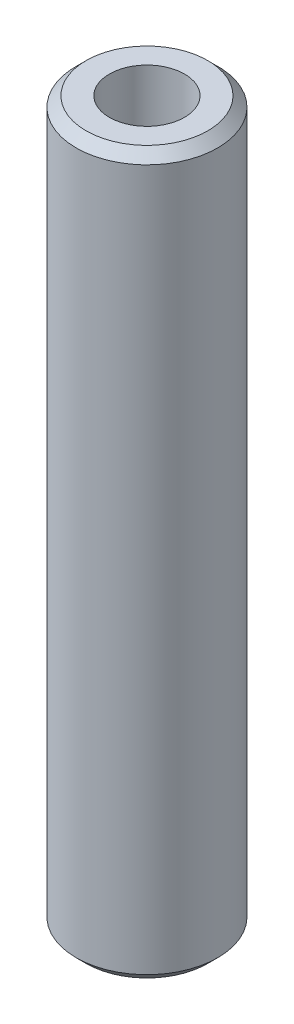
SolidWorks part; units mm, degrees
ref_plane "Front Plane" through (0, 0, 0) normal (0, 0, 1) x (1, 0, 0)
ref_plane "Top Plane" through (0, 0, 0) normal (0, 1, 0) x (1, 0, 0)
ref_plane "Right Plane" through (0, 0, 0) normal (1, 0, 0) x (0, 0, -1)
sketch "Sketch1" plane through (0, 0, 0) normal (0, 1, 0) x (1, 0, 0)
  circle A0 centre (0, 0) radius 17.5
  dimension "SHAFT_OD" = 35
extrude "Boss-Extrude1" add sketch "Sketch1" along normal blind 178.3565
sketch "Sketch2" plane through (0, 0, 0) normal (0, 1, 0) x (1, 0, 0)
  circle A0 centre (0, 0) radius 9.2911
  dimension "BORE_D" = 18.5822
extrude "Cut-Extrude1" cut sketch "Sketch2" along normal through all
chamfer "Chamfer1" distance 2.4467 angle 45 2 edges at (0, 178.3565, 17.5) (0, 0, 17.5)
